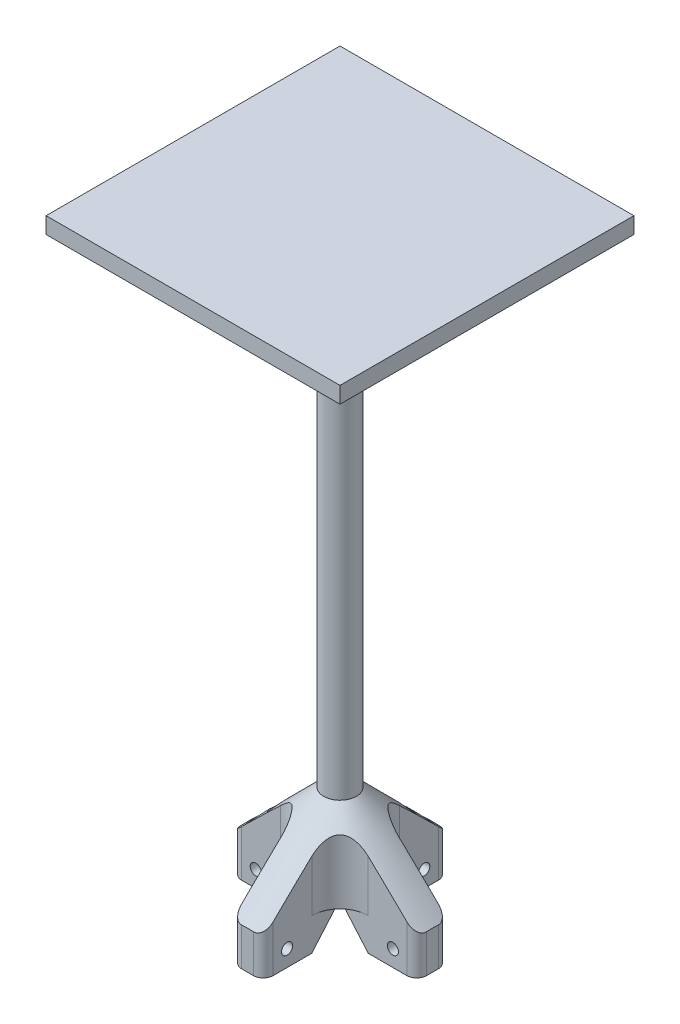
SolidWorks part; units mm, degrees
material "PLA"
ref_plane "Front Plane" through (0, 0, 0) normal (0, 0, 1) x (1, 0, 0)
ref_plane "Top Plane" through (0, 0, 0) normal (0, 1, 0) x (1, 0, 0)
ref_plane "Right Plane" through (0, 0, 0) normal (1, 0, 0) x (0, 0, -1)
sketch "Sketch8" plane through (0, 0, 0) normal (0, 1, 0) x (1, 0, 0)
  line L0 (13.7, 4.8) -> (28.3, 4.8)
  line L1 (-4.8, 13.7) -> (4.8, 13.7)
  line L2 (-4.8, 13.7) -> (-4.8, 28.3)
  line L3 (-4.8, 28.3) -> (4.8, 28.3)
  line L4 (4.8, 13.7) -> (4.8, 28.3)
  line L5 (-4.8, 13.7) -> (4.8, 28.3) construction
  line L6 (-4.8, 28.3) -> (4.8, 13.7) construction
  line L7 (13.7, 4.8) -> (13.7, -4.8)
  line L8 (13.7, -4.8) -> (28.3, -4.8)
  line L9 (28.3, 4.8) -> (28.3, -4.8)
  line L10 (4.8, -13.7) -> (4.8, -28.3)
  line L11 (4.8, -13.7) -> (-4.8, -13.7)
  line L12 (-4.8, -13.7) -> (-4.8, -28.3)
  line L13 (4.8, -28.3) -> (-4.8, -28.3)
  line L14 (-13.7, -4.8) -> (-28.3, -4.8)
  line L15 (-13.7, -4.8) -> (-13.7, 4.8)
  line L16 (-13.7, 4.8) -> (-28.3, 4.8)
  line L17 (-28.3, -4.8) -> (-28.3, 4.8)
  line L18 (-13.7, 4.8) -> (0, 4.8)
  line L19 (-13.7, -4.8) -> (0, -4.8)
  line L20 (4.8, 13.7) -> (4.8, 0)
  line L21 (-4.8, 13.7) -> (-4.8, 0)
  line L22 (13.7, -4.8) -> (0, -4.8)
  line L23 (13.7, 4.8) -> (0, 4.8)
  line L24 (-4.8, -13.7) -> (-4.8, 0)
  line L25 (4.8, -13.7) -> (4.8, 0)
  point P0 (0, 21)
  point P21 (0, 0)
  point P38 (0, 0)
  dimension "D1" = 21
  dimension "D2" = 9.6
  dimension "D3" = 4
  dimension "D5" = 14.6
  dimension "D4" = 4
extrude "Boss-Extrude4" add sketch "Sketch8" along normal blind 1.5 separate body contours L17 L14 L15 L16 | L1 L4 L3 L2 | L9 L0 L7 L8 | L13 L10 L11 L12 | L19 L24 L21 L18 L15 | L23 L20 L1 L21 L18 | L25 L22 L7 L23 L20 | L11 L25 L22 L19 L24 | L24 L19 | L18 L21 | L20 L23 | L22 L25 region at (21, 0, 0) region at (9.25, 0, 0) region at (0, 0, -9.25) region at (0, 0, 0) region at (0, 0, 9.25) region at (0, 0, -21) region at (0, 0, 21) region at (-9.25, 0, 0) region at (-21, 0, 0)
sketch "Sketch7" plane through (0, 1.5, 0) normal (0, 1, 0) x (1, 0, 0)
  circle A0 centre (0, 0) radius 5
  dimension "D1" = 10
extrude "Boss-Extrude3" add sketch "Sketch7" along normal blind 170
fillet "Fillet3" radius 8.65 4 edges at (4.8, 0.75, -4.8) (4.8, 0.75, 4.8) (-4.8, 0.75, 4.8) (-4.8, 0.75, -4.8)
sketch "Sketch13" plane through (0, 0, 0) normal (0, -1, 0) x (1, 0, 0)
  line L0 (-4.8, -28.3) -> (-4.8, -13.45) construction
  line L1 (-4.8, -28.3) -> (4.8, -28.3) construction
  line L2 (-4.8, -28.3) -> (-4.8, -13.45)
  line L3 (-4.8, -28.3) -> (4.8, -28.3)
  line L4 (4.8, -28.3) -> (4.8, -13.45) construction
  line L5 (-4.8, -28.3) -> (4.8, -28.3)
  line L6 (-4.8, -28.3) -> (-4.8, -13.45)
  line L7 (-4.8, -13.45) -> (4.8, -13.45)
  line L8 (4.8, -28.3) -> (4.8, -13.45)
  line L9 (-28.3, 4.8) -> (-13.45, 4.8)
  line L10 (-28.3, 4.8) -> (-28.3, -4.8)
  line L11 (-28.3, -4.8) -> (-13.45, -4.8)
  line L12 (-13.45, 4.8) -> (-13.45, -4.8)
  line L13 (4.8, 28.3) -> (4.8, 13.45)
  line L14 (4.8, 28.3) -> (-4.8, 28.3)
  line L15 (-4.8, 28.3) -> (-4.8, 13.45)
  line L16 (4.8, 13.45) -> (-4.8, 13.45)
  line L17 (28.3, -4.8) -> (13.45, -4.8)
  line L18 (28.3, -4.8) -> (28.3, 4.8)
  line L19 (28.3, 4.8) -> (13.45, 4.8)
  line L20 (13.45, -4.8) -> (13.45, 4.8)
  point P21 (0, 0)
  line M10 (-28.3, 4.8) -> (-28.3, -4.8)
  line M11 (-28.3, -4.8) -> (-13.45, -4.8)
  line M14 (-4.8, -28.3) -> (4.8, -28.3)
  line M15 (4.8, -28.3) -> (4.8, -13.45)
  line M17 (13.45, -4.8) -> (28.3, -4.8)
  line M18 (28.3, -4.8) -> (28.3, 4.8)
  line M19 (28.3, 4.8) -> (13.45, 4.8)
  line M21 (4.8, 13.45) -> (4.8, 28.3)
  line M22 (4.8, 28.3) -> (-4.8, 28.3)
  line M23 (-4.8, 28.3) -> (-4.8, 13.45)
  line M25 (-13.45, 4.8) -> (-28.3, 4.8)
  dimension "D1" = 14.85
  dimension "D2" = 4
extrude "Boss-Extrude7" add sketch "Sketch13" along normal blind 10 contours L7 L2 M14 M15 | L12 M25 M10 M11 | L16 M21 M22 M23 | L20 M17 M18 M19 region at (0, 0, -20.875) region at (-20.875, 0, 0) region at (0, 0, 20.875) region at (20.875, 0, 0)
hole_wizard "M3 Clearance Hole2" positions "Sketch9" profile "Sketch10" hole size "M3" standard "ANSI Metric" end condition up to next
sketch "Sketch9" plane through (-4.8, 2.575, 0) normal (1, 0, 0) x (0, -1, 0)
  line L2 (1.075, -4.8) -> (1.075, 4.8) construction
  line L3 (1.075, 5) -> (1.075, -5) construction
  line L4 (1.075, 5) -> (1.075, -5)
  line L7 (12.575, 13.45) -> (2.575, 13.45) construction
  line L8 (12.575, 13.45) -> (2.575, 13.45)
  point P15 (1.075, 0)
  point P38 (7.575, 21)
  point P45 (7.575, 13.45)
  dimension "D1" = 21
sketch "Sketch10" plane through (-4.8, -5, -21) normal (0, 1, 0) x (0, 0, 1)
  line L0 (0, 0) -> (0, 9.601)
  line L1 (0, 9.601) -> (1.7, 9.601)
  line L2 (1.7, 9.601) -> (1.7, 0)
  line L5 (1.7, 0) -> (0, 0)
  line L11 (0, -6.35) -> (0, 107.95) construction
  dimension "Thru Hole Dia." = 3.4
  dimension "Thru Hole Depth" = 9.601
pattern_circular "CirPattern1" count 4 over 360 about axis through (0, 171.5, 0) along (0, -1, 0) of "M3 Clearance Hole2" reverse direction yes
fillet "Fillet8" radius 3 8 edges at (4.8, -4.25, -28.3) (-4.8, -4.25, -28.3) (28.3, -4.25, -4.8) (28.3, -4.25, 4.8) (4.8, -4.25, 28.3) (-4.8, -4.25, 28.3) (-28.3, -4.25, 4.8) (-28.3, -4.25, -4.8)
sketch "Sketch11" plane through (0, 171.5, 0) normal (0, 1, 0) x (1, 0, 0)
  line L1 (-45, 45) -> (45, 45)
  line L2 (-45, 45) -> (-45, -45)
  line L3 (-45, -45) -> (45, -45)
  line L4 (45, 45) -> (45, -45)
  line L5 (-45, 45) -> (45, -45) construction
  line L6 (-45, -45) -> (45, 45) construction
  point P0 (0, 0)
  dimension "D1" = 90
extrude "Boss-Extrude5" add sketch "Sketch11" along normal blind 5
chamfer "Chamfer1" distance 23.5 angle 45 1 edges at (0, 1.5, 5)
fillet "Fillet5" radius 20 1 edges at (0, 171.5, 5)
chamfer "Chamfer2" distance 10 distance2 8.6 4 edges at (13.45, 0, 0) (0, 0, 13.45) (-13.45, 0, 0) (0, 0, -13.45) first distance on face at (13.45, -5, 0) first distance on face at (0, -5, 13.45) first distance on face at (-13.45, -5, 0) first distance on face at (0, -5, -13.45)
sketch "Sketch14" plane through (0, 0, 0) normal (0, -1, 0) x (1, 0, 0)
  circle A0 centre (0, 0) radius 5 construction
  circle A1 centre (0, 0) radius 5
  circle A2 centre (0, 0) radius 2.075
  dimension "D1" = 4.15
extrude "Cut-Extrude1" cut sketch "Sketch14" against normal offset from surface (174.5 mm away) 2 contours A2 region at (0, 0, 0) up to face at (0, 176.5, 0)
